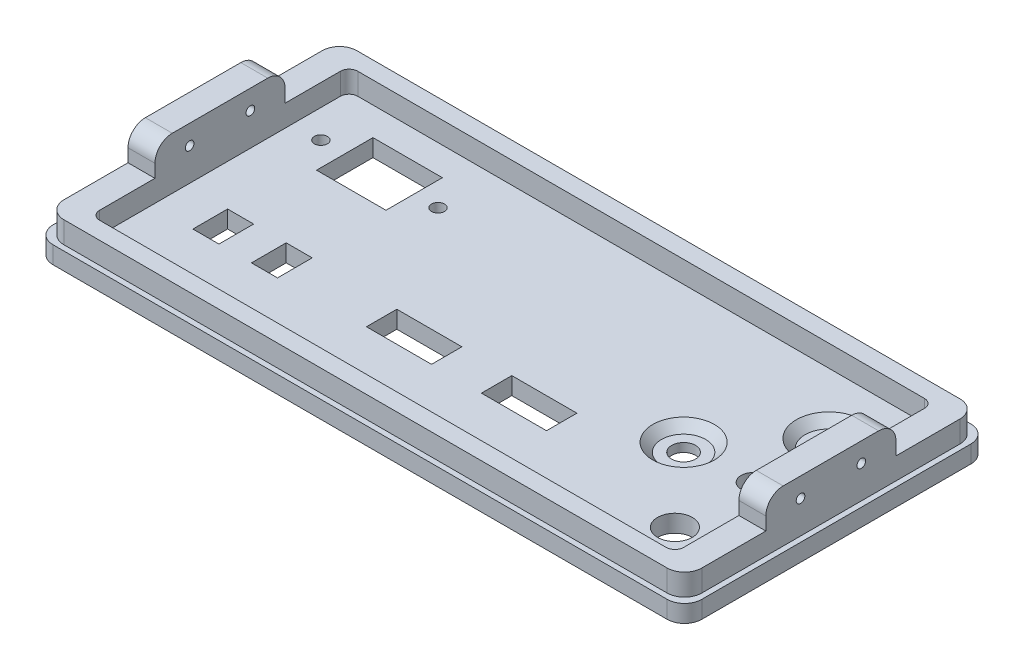
SolidWorks part; units mm, degrees
ref_plane "Front Plane" through (0, 0, 0) normal (0, 0, 1) x (1, 0, 0)
ref_plane "Top Plane" through (0, 0, 0) normal (0, 1, 0) x (1, 0, 0)
ref_plane "Right Plane" through (0, 0, 0) normal (1, 0, 0) x (0, 0, -1)
sketch "Sketch1" plane through (0, 0, 0) normal (0, 1, 0) x (1, 0, 0)
  line L1 (-74.75, 35) -> (74.75, 35)
  line L2 (-74.75, 35) -> (-74.75, -35)
  line L3 (-74.75, -35) -> (74.75, -35)
  line L4 (74.75, 35) -> (74.75, -35)
  line L5 (-74.75, 35) -> (74.75, -35) construction
  line L6 (-74.75, -35) -> (74.75, 35) construction
  point P0 (0, 0)
  dimension "D1" = 70
  dimension "D2" = 149.5
extrude "Boss-Extrude1" add sketch "Sketch1" along normal blind 4
fillet "Fillet1" radius 4 4 edges at (-74.75, 2, -35) (-74.75, 2, 35) (74.75, 2, -35) (74.75, 2, 35)
sketch "Sketch6" plane through (0, 4, 0) normal (0, 1, 0) x (1, 0, 0)
  line L1 (-73.5, 33.75) -> (73.5, 33.75)
  line L2 (-73.5, 33.75) -> (-73.5, -33.75)
  line L3 (-73.5, -33.75) -> (73.5, -33.75)
  line L4 (73.5, 33.75) -> (73.5, -33.75)
  line L5 (-73.5, 33.75) -> (73.5, -33.75) construction
  line L6 (-73.5, -33.75) -> (73.5, 33.75) construction
  point P0 (0, 0)
  dimension "D1" = 67.5
  dimension "D2" = 147
extrude "Boss-Extrude3" add sketch "Sketch6" along normal blind 5
fillet "Fillet2" radius 4 4 edges at (-73.5, 6.5, 33.75) (73.5, 6.5, 33.75) (73.5, 6.5, -33.75) (-73.5, 6.5, -33.75)
sketch "Sketch7" plane through (0, 9, 0) normal (0, 1, 0) x (1, 0, 0)
  line L0 (-73.5, 0) -> (0, 0) construction
  line L1 (-73.5, 29.75) -> (-73.5, -29.75) construction
  line L2 (0, 0) -> (0, 33.75) construction
  line L3 (69.5, 33.75) -> (-69.5, 33.75) construction
  line L4 (-73.5, -15) -> (-73.5, 15)
  line L5 (-73.5, 29.75) -> (-73.5, -29.75) construction
  line L6 (-73.5, 15) -> (-67.2945, 15)
  line L7 (-67.2945, 15) -> (-67.2945, -15)
  line L8 (-73.5, -15) -> (-67.2945, -15)
  line L9 (73.5, 15) -> (67.2945, 15)
  line L10 (73.5, -15) -> (73.5, 15)
  line L11 (73.5, -15) -> (67.2945, -15)
  line L12 (67.2945, 15) -> (67.2945, -15)
  point P14 (-67.2945, 0)
  dimension "D1" = 15
extrude "Boss-Extrude4" add sketch "Sketch7" along normal blind 7
sketch "Sketch8" plane through (-73.5, 0, 0) normal (-1, 0, 0) x (0, 0, 1)
  line L0 (0, 16) -> (0, 0) construction
  line L1 (-15, 16) -> (15, 16) construction
  circle A0 centre (-7, 11.5) radius 1
  circle A1 centre (7, 11.5) radius 1
  dimension "D1" = 2
  dimension "D2" = 4.5
  dimension "D3" = 14
extrude "Cut-Extrude3" cut sketch "Sketch8" against normal through all
fillet "Fillet5" radius 4 4 edges at (70.3973, 16, 15) (70.3973, 16, -15) (-70.3973, 16, 15) (-70.3973, 16, -15)
sketch "Sketch9" plane through (0, 9, 0) normal (0, 1, 0) x (1, 0, 0)
  line L0 (69.5, 33.75) -> (-69.5, 33.75) construction
  line L1 (-67.2945, 29.75) -> (67.2945, 29.75)
  line L2 (-67.2945, 29.75) -> (-67.2945, -29.75)
  line L3 (-67.2945, -29.75) -> (67.2945, -29.75)
  line L4 (67.2945, 29.75) -> (67.2945, -29.75)
  line L5 (-67.2945, 29.75) -> (67.2945, -29.75) construction
  line L6 (-67.2945, -29.75) -> (67.2945, 29.75) construction
  line L7 (-67.2945, -15) -> (-67.2945, 15) construction
  point P0 (0, 0)
  dimension "D1" = 4
  dimension "D2" = 0
extrude "Cut-Extrude4" cut sketch "Sketch9" against normal blind 5
fillet "Fillet7" radius 2 4 edges at (67.2945, 6.5, 29.75) (-67.2945, 6.5, 29.75) (67.2945, 6.5, -29.75) (-67.2945, 6.5, -29.75)
sketch "Sketch11" plane through (0, 4, 0) normal (0, 1, 0) x (1, 0, 0)
  line L0 (-65.2945, -29.75) -> (65.2945, -29.75) construction
  line L1 (67.2945, -27.75) -> (67.2945, -15) construction
  circle A0 centre (57.2945, -19.75) radius 4
  dimension "D1" = 8
  dimension "D2" = 10
  dimension "D3" = 10
extrude "Cut-Extrude5" cut sketch "Sketch11" against normal through all
sketch "Sketch12" plane through (0, 4, 0) normal (0, 1, 0) x (1, 0, 0)
  line L0 (67.2945, 11) -> (67.2945, -11) construction
  line L1 (-65.2945, -29.75) -> (65.2945, -29.75) construction
  circle A0 centre (57.2945, -1.75) radius 2.75
  dimension "D1" = 5.5
  dimension "D2" = 10
  dimension "D3" = 28
extrude "Cut-Extrude6" cut sketch "Sketch12" against normal through all
sketch "Sketch13" plane through (0, 4, 0) normal (0, 1, 0) x (1, 0, 0)
  line L0 (67.2945, -27.75) -> (67.2945, 27.75) construction
  line L1 (65.2945, 29.75) -> (-65.2945, 29.75) construction
  circle A0 centre (57.2945, 15.75) radius 2.75
  dimension "D1" = 5.5
  dimension "D2" = 10
  dimension "D3" = 14
extrude "Cut-Extrude7" cut sketch "Sketch13" against normal through all
sketch "Sketch17" plane through (0, 4, 0) normal (0, 1, 0) x (1, 0, 0)
  line L0 (-67.2945, 27.75) -> (-67.2945, 15) construction
  line L1 (-55.2945, 23.25) -> (-39.2945, 23.25)
  line L2 (-55.2945, 23.25) -> (-55.2945, 10.25)
  line L3 (-55.2945, 10.25) -> (-39.2945, 10.25)
  line L4 (-39.2945, 23.25) -> (-39.2945, 10.25)
  line L5 (-55.2945, 23.25) -> (-39.2945, 10.25) construction
  line L6 (-55.2945, 10.25) -> (-39.2945, 23.25) construction
  line L7 (65.2945, 29.75) -> (-65.2945, 29.75) construction
  point P0 (-47.2945, 16.75)
  dimension "D1" = 16
  dimension "D2" = 13
  dimension "D3" = 20
  dimension "D4" = 13
extrude "Cut-Extrude11" cut sketch "Sketch17" against normal through all
sketch "Sketch18" plane through (0, 4, 0) normal (0, 1, 0) x (1, 0, 0)
  line L0 (-65.2945, -29.75) -> (65.2945, -29.75) construction
  line L1 (8.2055, -8.25) -> (23.2055, -8.25)
  line L2 (8.2055, -8.25) -> (8.2055, -15.25)
  line L3 (8.2055, -15.25) -> (23.2055, -15.25)
  line L4 (23.2055, -8.25) -> (23.2055, -15.25)
  line L5 (8.2055, -8.25) -> (23.2055, -15.25) construction
  line L6 (8.2055, -15.25) -> (23.2055, -8.25) construction
  line L7 (-67.2945, 27.75) -> (-67.2945, -27.75) construction
  line L9 (-18.2945, -8.25) -> (-3.2945, -8.25)
  line L10 (-18.2945, -8.25) -> (-18.2945, -15.25)
  line L11 (-18.2945, -15.25) -> (-3.2945, -15.25)
  line L12 (-3.2945, -8.25) -> (-3.2945, -15.25)
  line L13 (-18.2945, -8.25) -> (-3.2945, -15.25) construction
  line L14 (-18.2945, -15.25) -> (-3.2945, -8.25) construction
  circle A0 centre (-41.2945, -11.75) radius 3
  circle A1 centre (-54.7945, -11.75) radius 3
  point P0 (15.7055, -11.75)
  point P9 (-10.7945, -11.75)
  dimension "D9" = 6
  dimension "D10" = 6
  dimension "D1" = 15
  dimension "D2" = 7
  dimension "D3" = 18
  dimension "D4" = 83
  dimension "D5" = 15
  dimension "D6" = 7
  dimension "D7" = 11.5
  dimension "D8" = 18
  dimension "D11" = 23
  dimension "D12" = 13.5
  dimension "D13" = 18
extrude "Cut-Extrude12" cut sketch "Sketch18" against normal through all
sketch "Sketch19" plane through (0, 4, 0) normal (0, 1, 0) x (1, 0, 0)
  line L1 (-44.2945, -7.75) -> (-38.2945, -7.75)
  line L2 (-44.2945, -7.75) -> (-44.2945, -15.75)
  line L3 (-44.2945, -15.75) -> (-38.2945, -15.75)
  line L4 (-38.2945, -7.75) -> (-38.2945, -15.75)
  line L5 (-44.2945, -7.75) -> (-38.2945, -15.75) construction
  line L6 (-44.2945, -15.75) -> (-38.2945, -7.75) construction
  line L7 (-57.7945, -7.75) -> (-51.7945, -7.75)
  line L8 (-57.7945, -7.75) -> (-57.7945, -15.75)
  line L9 (-57.7945, -15.75) -> (-51.7945, -15.75)
  line L10 (-51.7945, -7.75) -> (-51.7945, -15.75)
  line L11 (-57.7945, -7.75) -> (-51.7945, -15.75) construction
  line L12 (-57.7945, -15.75) -> (-51.7945, -7.75) construction
  point P0 (-41.2945, -11.75)
  point P6 (-54.7945, -11.75)
  dimension "D1" = 6
  dimension "D2" = 8
  dimension "D3" = 6
  dimension "D4" = 8
extrude "Cut-Extrude13" cut sketch "Sketch19" against normal through all
sketch "Sketch20" plane through (0, 4, 0) normal (0, 1, 0) x (1, 0, 0)
  line L0 (-47.2945, 23.25) -> (-47.2945, 10.25) construction
  line L1 (-39.2945, 23.25) -> (-55.2945, 23.25) construction
  line L2 (-55.2945, 10.25) -> (-39.2945, 10.25) construction
  line L3 (-47.2945, 16.75) -> (-64.9319, 16.75) construction
  circle A0 centre (-60.7945, 16.75) radius 1.5
  circle A1 centre (-33.7945, 16.75) radius 1.5
  dimension "D1" = 3
  dimension "D2" = 13.5
extrude "Cut-Extrude14" cut sketch "Sketch20" against normal through all
sketch "Sketch22" plane through (0, 4, 0) normal (0, 1, 0) x (1, 0, 0)
  circle A0 centre (57.2945, 15.75) radius 5.5
  dimension "D1" = 11
extrude "Cut-Extrude15" cut sketch "Sketch22" against normal blind 2
chamfer "Chamfer2" distance 2 angle 45 1 edges at (57.2945, 4, -10.25)
sketch "Sketch23" plane through (0, 4, 0) normal (0, 1, 0) x (1, 0, 0)
  line L0 (-65.2945, -29.75) -> (65.2945, -29.75) construction
  line L1 (67.2945, -27.75) -> (67.2945, 27.75) construction
  circle A0 centre (41.2945, -1.75) radius 2.75
  dimension "D3" = 5.5
  dimension "D1" = 28
  dimension "D2" = 26
extrude "Cut-Extrude16" cut sketch "Sketch23" against normal through all
sketch "Sketch24" plane through (0, 4, 0) normal (0, 1, 0) x (1, 0, 0)
  circle A0 centre (41.2945, -1.75) radius 5.1
  dimension "D1" = 10.2
extrude "Cut-Extrude17" cut sketch "Sketch24" against normal blind 2
chamfer "Chamfer3" distance 2 angle 45 1 edges at (41.2945, 4, 6.85)
